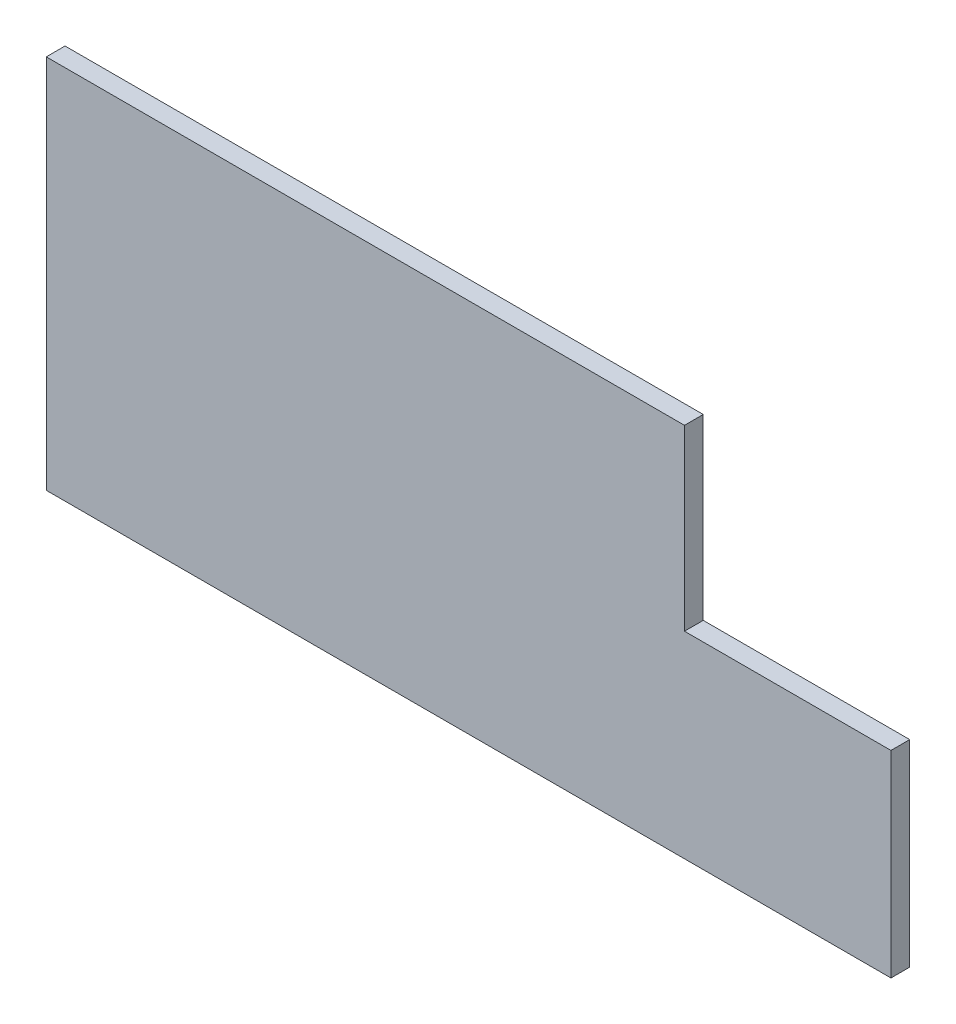
SolidWorks part; units mm, degrees
ref_plane "Plan de face" through (0, 0, 0) normal (0, 0, 1) x (1, 0, 0)
ref_plane "Plan de dessus" through (0, 0, 0) normal (0, 1, 0) x (1, 0, 0)
ref_plane "Plan de droite" through (0, 0, 0) normal (1, 0, 0) x (0, 0, -1)
sketch "Esquisse1" plane through (0, 0, 0) normal (0, 0, 1) x (1, 0, 0)
  line L1 (-103.5883, 48.6413) -> (66.4117, 48.6413)
  line L2 (-103.5883, 48.6413) -> (-103.5883, -51.3587)
  line L3 (-103.5883, -51.3587) -> (66.4117, -51.3587)
  line L4 (66.4117, 48.6413) -> (66.4117, -51.3587)
  dimension "D1" = 100
  dimension "D2" = 170
extrude "Boss.-Extru.1" add sketch "Esquisse1" along normal blind 5
sketch "Esquisse2" plane through (66.4117, 0, 0) normal (1, 0, 0) x (0, 0, -1)
  line L0 (0, -51.3587) -> (0, 48.6413) construction
  line L1 (-5, 1.1413) -> (0, 1.1413)
  line L2 (-5, 1.1413) -> (-5, -51.3587)
  line L3 (-5, -51.3587) -> (0, -51.3587)
  line L4 (0, 1.1413) -> (0, -51.3587)
  line L5 (-5, -51.3587) -> (0, -51.3587) construction
  dimension "D1" = 52.5
extrude "Boss.-Extru.2" add sketch "Esquisse2" along normal blind 55
